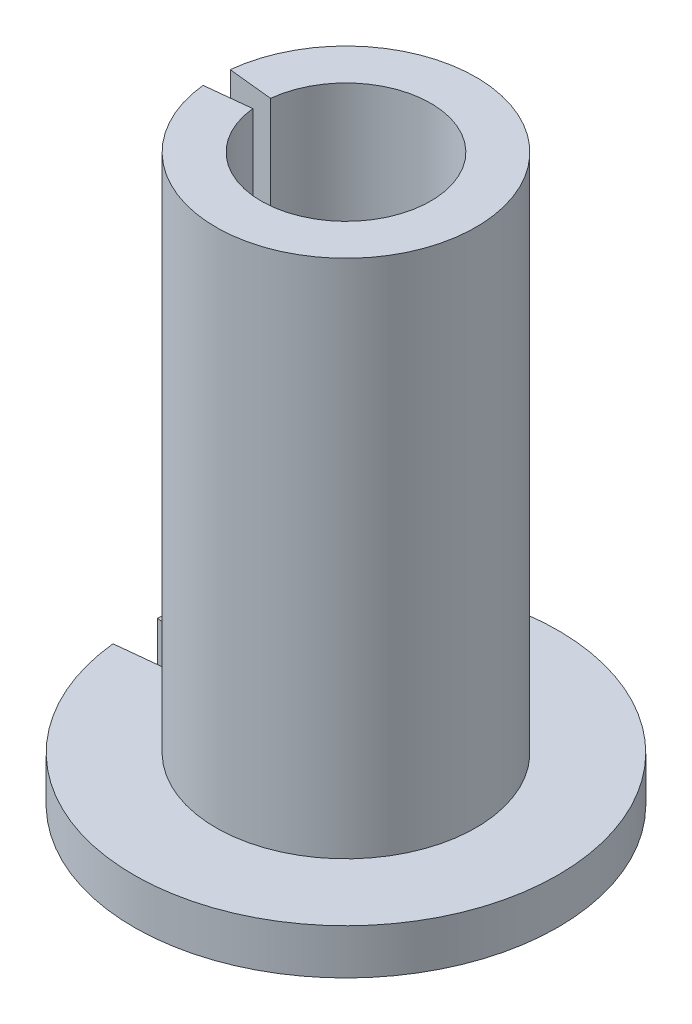
SolidWorks part; units mm, degrees
ref_plane "Front Plane" through (0, 0, 0) normal (0, 0, 1) x (1, 0, 0)
ref_plane "Top Plane" through (0, 0, 0) normal (0, 1, 0) x (1, 0, 0)
ref_plane "Right Plane" through (0, 0, 0) normal (1, 0, 0) x (0, 0, -1)
sketch "Sketch1" plane through (0, 0, 0) normal (0, 0, 1) x (1, 0, 0)
  line L0 (0, 0) -> (0, 20) construction
  line L1 (3, 20) -> (3, 0)
  line L2 (3, 0) -> (7.5, 0)
  line L3 (7.5, 0) -> (7.5, 1.6)
  line L4 (7.5, 1.6) -> (4.6, 1.6)
  line L5 (4.6, 1.6) -> (4.6, 20)
  line L6 (4.6, 20) -> (3, 20)
  dimension "D1" = 20
  dimension "D2" = 1.6
  dimension "D3" = 9.2
  dimension "D4" = 15
revolve "Revolve1" add sketch "Sketch1" angle 348 mid plane about L0
sketch "Sketch2" plane through (0, 0, 0) normal (0, 1, 0) x (1, 0, 0)
  line L0 (0, 0) -> (-7.5, 0) construction
  line L1 (-7.5, 0) -> (-5.964, -4.5476) construction
  line L2 (-5.964, -4.5476) -> (0, 0) construction
  circle A2 centre (0, 0) radius 7.5 construction
  circle A3 centre (0, 0) radius 7.5
  dimension "D1" = 4.8
  dimension "D2" = 37.326
equation "\"D1@Revolve1\"=360-12"
